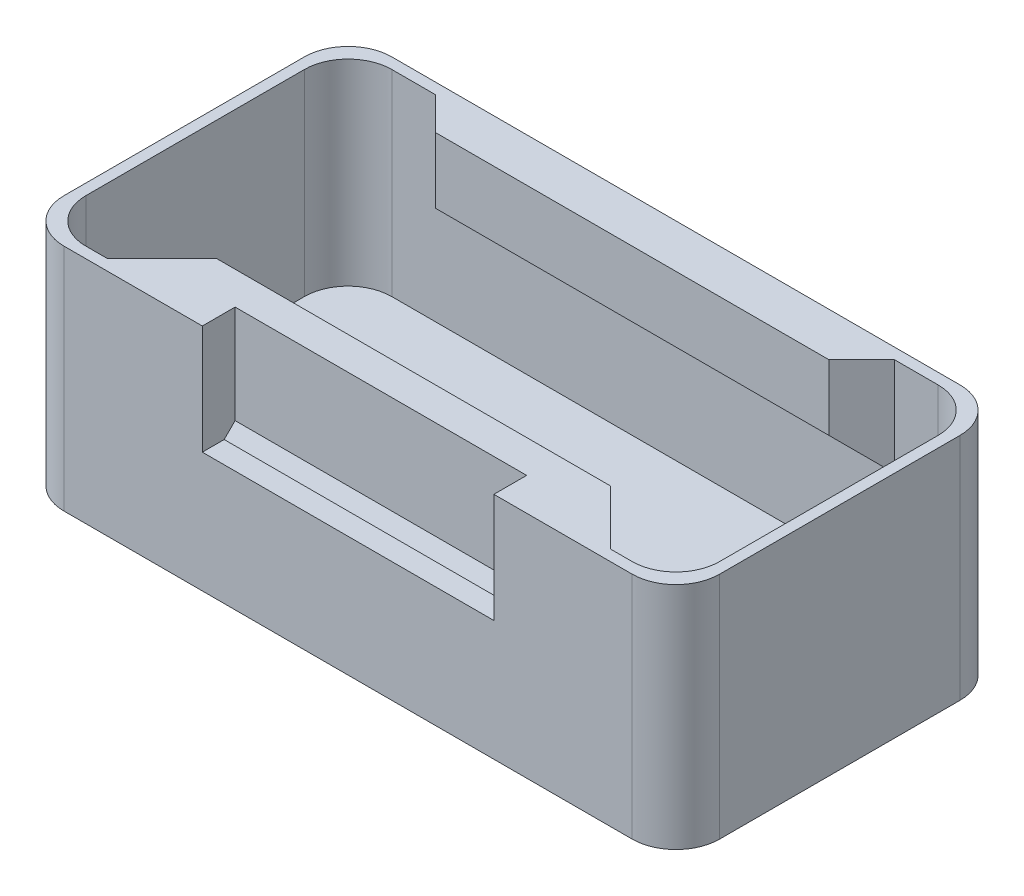
SolidWorks part; units mm, degrees
ref_plane "Front Plane" through (0, 0, 0) normal (0, 0, 1) x (1, 0, 0)
ref_plane "Top Plane" through (0, 0, 0) normal (0, 1, 0) x (1, 0, 0)
ref_plane "Right Plane" through (0, 0, 0) normal (1, 0, 0) x (0, 0, -1)
sketch "Sketch1" plane through (0, 0, 0) normal (0, 1, 0) x (1, 0, 0)
  line L1 (0, 0) -> (300, 0)
  line L2 (0, 0) -> (0, 150)
  line L3 (0, 150) -> (300, 150)
  line L4 (300, 0) -> (300, 150)
  dimension "D1" = 300
  dimension "D2" = 150
extrude "Boss-Extrude1" add sketch "Sketch1" along normal blind 5
sketch "Sketch3" plane through (0, 5, 0) normal (0, 1, 0) x (1, 0, 0)
  line L8 (5, 145) -> (5, 5)
  line L9 (5, 5) -> (295, 5)
  line L10 (295, 5) -> (295, 145)
  line L11 (295, 145) -> (5, 145)
  line L12 (5, 145) -> (5, 5)
  line L13 (5, 5) -> (295, 5)
  line L14 (295, 5) -> (295, 145)
  line L15 (295, 145) -> (5, 145)
  line L16 (0, 150) -> (0, 0)
  line L17 (0, 0) -> (300, 0)
  line L18 (300, 0) -> (300, 150)
  line L19 (300, 150) -> (0, 150)
  line L20 (0, 150) -> (0, 0)
  line L21 (0, 0) -> (300, 0)
  line L22 (300, 0) -> (300, 150)
  line L23 (300, 150) -> (0, 150)
  dimension "D1" = 5
  dimension "D2" = 0
extrude "Boss-Extrude2" add sketch "Sketch3" along normal blind 100
sketch "Sketch4" plane through (0, 5, 0) normal (0, 1, 0) x (1, 0, 0)
  line L0 (5, 145) -> (5, 5) construction
  line L1 (5, 65) -> (295, 65)
  line L2 (5, 65) -> (5, 95)
  line L3 (5, 95) -> (295, 95)
  line L4 (295, 65) -> (295, 95)
  line L5 (295, 5) -> (295, 145) construction
  line L6 (295, 145) -> (5, 145) construction
  line L15 (295, 5) -> (295, 145)
  line L16 (295, 145) -> (5, 145)
  line L17 (5, 145) -> (5, 5)
  line L18 (5, 5) -> (295, 5)
  line L19 (295, 5) -> (295, 145)
  line L20 (295, 145) -> (5, 145)
  line L21 (5, 145) -> (5, 5)
  line L22 (5, 5) -> (295, 5)
  line M3 (295, 5) -> (295, 145)
  line M4 (295, 145) -> (5, 145)
  line M5 (5, 145) -> (5, 5)
  line M6 (5, 5) -> (295, 5)
  dimension "D1" = 30
  dimension "D2" = 50
  dimension "D3" = 0
extrude "Boss-Extrude3" add sketch "Sketch4" along normal blind 10 contours L3 M5 M3 M4 | L1 M5 M6 M3 region at (150, 5, -35) region at (150, 5, -120)
sketch "Sketch7" plane through (0, 5, 0) normal (0, 1, 0) x (1, 0, 0)
  line L0 (150, 65) -> (150, 95) construction
  line L1 (5, 80) -> (247.227, 80) construction
  line L4 (5, 95) -> (5, 65)
  line L5 (5, 65) -> (295, 65)
  line L6 (295, 65) -> (295, 95)
  line L7 (295, 95) -> (5, 95)
  line L8 (5, 95) -> (5, 65)
  line L9 (5, 65) -> (295, 65)
  line L10 (295, 65) -> (295, 95)
  line L11 (295, 95) -> (5, 95)
  circle A0 centre (150, 80) radius 12
  point P10 (125, 80)
  dimension "D4" = 24
  dimension "D1" = 0
extrude "Cut-Extrude1" cut sketch "Sketch7" against normal through all contours A0
fillet "Fillet1" radius 20 8 edges at (300, 52.5, 0) (300, 52.5, -150) (0, 52.5, -150) (0, 52.5, 0) (295, 60, -145) (295, 60, -5) (5, 60, -5) (5, 60, -145)
sketch "Sketch10" plane through (0, 0, -145) normal (0, 0, 1) x (1, 0, 0)
  line L0 (275, 105) -> (25, 105) construction
  line L1 (60, 105) -> (240, 105)
  line L2 (60, 105) -> (60, 75)
  line L3 (60, 75) -> (240, 75)
  line L4 (240, 105) -> (240, 75)
  point P6 (150, 75)
  point P7 (150, 105)
  point P8 (0, 0)
  point P9 (0, 0)
  dimension "D1" = 180
  dimension "D2" = 30
extrude "Boss-Extrude4" add sketch "Sketch10" along normal blind 15
sketch "Sketch11" plane through (0, 0, -5) normal (0, 0, -1) x (-1, 0, 0)
  line L0 (-25, 105) -> (-275, 105) construction
  line L1 (-60, 105) -> (-240, 105)
  line L2 (-60, 105) -> (-60, 75)
  line L3 (-60, 75) -> (-240, 75)
  line L4 (-240, 105) -> (-240, 75)
  point P6 (-150, 75)
  point P7 (-150, 105)
  point P8 (0, 0)
  dimension "D1" = 180
  dimension "D2" = 30
extrude "Boss-Extrude5" add sketch "Sketch11" along normal blind 25
chamfer "Chamfer2" distance 15 angle 45 3 edges at (240, 90, -145) (150, 75, -145) (60, 90, -145)
chamfer "Chamfer3" distance 25 angle 45 3 edges at (60, 90, -5) (150, 75, -5) (240, 90, -5)
sketch "Sketch12" plane through (0, 105, 0) normal (0, 1, 0) x (1, 0, 0)
  line L0 (20, 0) -> (280, 0) construction
  line L1 (83.2978, 0) -> (216.7022, 0)
  line L2 (83.2978, 0) -> (83.2978, 15)
  line L3 (83.2978, 15) -> (216.7022, 15)
  line L4 (216.7022, 0) -> (216.7022, 15)
  line L9 (20, 0) -> (280, 0)
  line L10 (300, 20) -> (300, 130)
  line L11 (280, 150) -> (20, 150)
  line L12 (0, 130) -> (0, 20)
  line L13 (20, 0) -> (280, 0)
  line L14 (300, 20) -> (300, 130)
  line L15 (280, 150) -> (20, 150)
  line L16 (0, 130) -> (0, 20)
  arc A4 (280, 0) -> (300, 20) centre (280, 20) ccw
  arc A5 (300, 130) -> (280, 150) centre (280, 130) ccw
  arc A6 (20, 150) -> (0, 130) centre (20, 130) ccw
  arc A7 (0, 20) -> (20, 0) centre (20, 20) ccw
  arc A8 (280, 0) -> (300, 20) centre (280, 20) ccw
  arc A9 (300, 130) -> (280, 150) centre (280, 130) ccw
  arc A10 (20, 150) -> (0, 130) centre (20, 130) ccw
  arc A11 (0, 20) -> (20, 0) centre (20, 20) ccw
  point P6 (150, 0)
  point P9 (150, 0)
  point P10 (0, 0)
  line M10 (20, 0) -> (280, 0)
  dimension "D2" = 15
  dimension "D1" = 0
extrude "Cut-Extrude2" cut sketch "Sketch12" against normal blind 50 contours L4 L3 L2 M10 region at (150, 105, -7.5)
